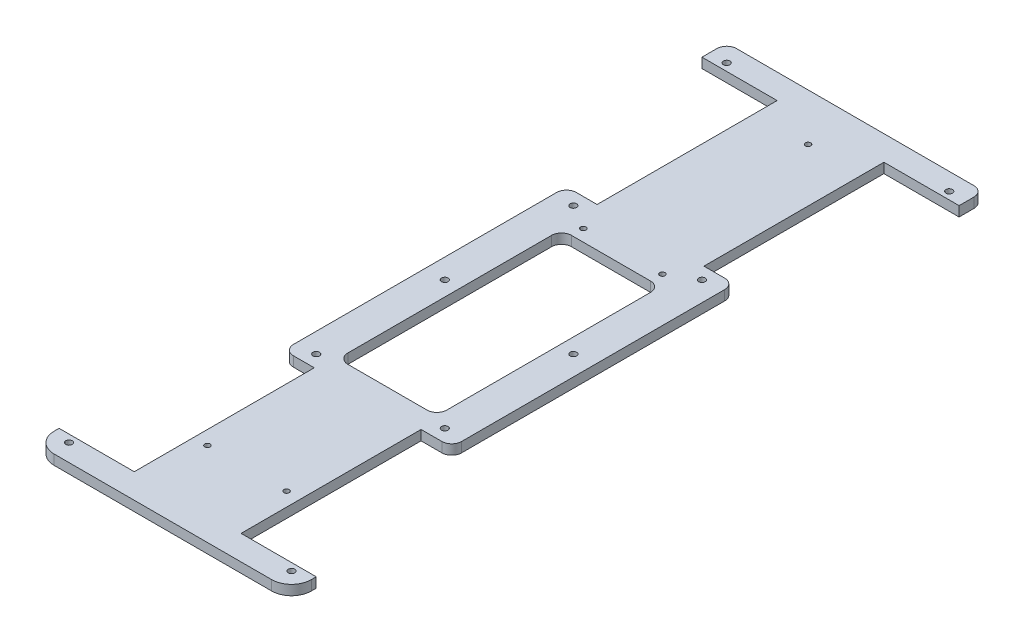
SolidWorks part; units mm, degrees
ref_plane "Front Plane" through (0, 0, 0) normal (0, 0, 1) x (1, 0, 0)
ref_plane "Top Plane" through (0, 0, 0) normal (0, 1, 0) x (1, 0, 0)
ref_plane "Right Plane" through (0, 0, 0) normal (1, 0, 0) x (0, 0, -1)
sketch "Sketch1" plane through (0, 0, 0) normal (0, 1, 0) x (1, 0, 0)
  line L0 (0, 0) -> (130, 0)
  line L1 (0, 0) -> (130, 0) construction
  line L2 (0, 0) -> (0, 350) construction
  line L3 (0, 350) -> (130, 350) construction
  line L4 (130, 0) -> (130, 350) construction
  line L5 (130, 0) -> (130, 12.5)
  line L6 (130, 12.5) -> (92, 12.5)
  line L7 (92, 12.5) -> (92, 103.5)
  line L11 (92, 246.5) -> (92, 337.5)
  line L12 (92, 337.5) -> (130, 337.5)
  line L13 (130, 337.5) -> (130, 350)
  line L14 (130, 350) -> (0, 350)
  line L15 (0, 350) -> (0, 337.5)
  line L16 (0, 337.5) -> (38, 337.5)
  line L17 (38, 337.5) -> (38, 246.5)
  line L21 (38, 103.5) -> (38, 12.5)
  line L22 (38, 12.5) -> (0, 12.5)
  line L23 (0, 12.5) -> (0, 0)
  line L24 (38, 246.5) -> (22.5, 246.5)
  line L25 (22.5, 246.5) -> (22.5, 103.5)
  line L26 (22.5, 103.5) -> (38, 103.5)
  line L27 (92, 246.5) -> (107.5, 246.5)
  line L28 (107.5, 246.5) -> (107.5, 103.5)
  line L29 (107.5, 103.5) -> (92, 103.5)
  dimension "D1" = 130
  dimension "D2" = 350
  dimension "D3" = 38
  dimension "D4" = 91
  dimension "D5" = 22.5
  dimension "D6" = 143
extrude "Boss-Extrude1" add sketch "Sketch1" along normal blind 5
fillet "Fillet1" radius 10 2 edges at (130, 2.5, 0) (0, 2.5, 0)
fillet "Fillet2" radius 5 6 edges at (0, 2.5, -350) (130, 2.5, -350) (107.5, 2.5, -246.5) (107.5, 2.5, -103.5) (22.5, 2.5, -103.5) (22.5, 2.5, -246.5)
sketch "Sketch2" plane through (0, 5, 0) normal (0, 1, 0) x (1, 0, 0)
  line L2 (32.5, 240) -> (32.5, 110) construction
  line L3 (22.5, 175) -> (32.5, 175) construction
  line L4 (22.5, 241.5) -> (22.5, 108.5) construction
  line L5 (65, 350) -> (65, 0) construction
  line L6 (125, 350) -> (5, 350) construction
  line L7 (10, 0) -> (120, 0) construction
  circle A0 centre (32.5, 240) radius 1.65
  circle A1 centre (32.5, 175) radius 1.65
  circle A2 centre (32.5, 110) radius 1.65
  circle A3 centre (97.5, 110) radius 1.65
  circle A4 centre (97.5, 175) radius 1.65
  circle A5 centre (97.5, 240) radius 1.65
  dimension "D3" = 3.3
  dimension "D1" = 10
  dimension "D2" = 130
extrude "Cut-Extrude1" cut sketch "Sketch2" against normal through all
sketch "Sketch3" plane through (0, 5, 0) normal (0, 1, 0) x (1, 0, 0)
  line L0 (0, 12.5) -> (8.75, 12.5) construction
  line L1 (38, 12.5) -> (0, 12.5) construction
  line L2 (8.75, 12.5) -> (8.75, 8.75) construction
  line L3 (65, 0) -> (65, 57.6288) construction
  line L4 (10, 0) -> (120, 0) construction
  circle A0 centre (8.75, 8.75) radius 1.65
  circle A1 centre (121.25, 8.75) radius 1.65
  dimension "D3" = 3.3
  dimension "D1" = 8.75
  dimension "D2" = 3.75
extrude "Cut-Extrude2" cut sketch "Sketch3" against normal through all
sketch "Sketch4" plane through (0, 5, 0) normal (0, 1, 0) x (1, 0, 0)
  line L0 (0, 337.5) -> (8.75, 337.5) construction
  line L1 (0, 337.5) -> (38, 337.5) construction
  line L2 (8.75, 337.5) -> (8.75, 341.25) construction
  line L3 (65, 350) -> (65, 288.2737) construction
  line L4 (125, 350) -> (5, 350) construction
  circle A0 centre (8.75, 341.25) radius 1.65
  circle A1 centre (121.25, 341.25) radius 1.65
  dimension "D3" = 3.3
  dimension "D1" = 8.75
  dimension "D2" = 3.75
extrude "Cut-Extrude3" cut sketch "Sketch4" against normal through all
sketch "Sketch5" plane through (0, 5, 0) normal (0, 1, 0) x (1, 0, 0)
  line L0 (38, 12.5) -> (92, 12.5) construction
  line L1 (65, 12.5) -> (65, 42.5) construction
  line L2 (45, 42.5) -> (85, 42.5) construction
  line L3 (65, 42.5) -> (65, 232.5) construction
  line L4 (45, 232.5) -> (85, 232.5) construction
  line L5 (65, 350) -> (65, 326.15) construction
  line L6 (125, 350) -> (5, 350) construction
  circle A0 centre (45, 42.5) radius 1.35
  circle A1 centre (85, 42.5) radius 1.35
  circle A2 centre (45, 232.5) radius 1.35
  circle A3 centre (85, 232.5) radius 1.35
  circle A4 centre (65, 326.15) radius 1.35
  point P8 (65, 42.5)
  point P14 (65, 232.5)
  dimension "D3" = 2.7
  dimension "D1" = 30
  dimension "D2" = 40
  dimension "D4" = 190
  dimension "D5" = 40
  dimension "D6" = 23.85
extrude "Cut-Extrude4" cut sketch "Sketch5" against normal blind 10
sketch "Sketch6" plane through (0, 5, 0) normal (0, 1, 0) x (1, 0, 0)
  line L0 (38, 246.5) -> (92, 246.5) construction
  line L1 (40, 226.5) -> (90, 226.5)
  line L2 (40, 226.5) -> (40, 113.5)
  line L3 (40, 113.5) -> (90, 113.5)
  line L4 (90, 226.5) -> (90, 113.5)
  line L5 (38, 103.5) -> (92, 103.5) construction
  line L6 (65, 246.5) -> (65, 103.5) construction
  point P13 (65, 113.5)
  point P16 (65, 103.5)
  dimension "D1" = 20
  dimension "D2" = 10
  dimension "D3" = 50
extrude "Cut-Extrude5" cut sketch "Sketch6" against normal blind 10
fillet "Fillet4" radius 5 4 edges at (90, 2.5, -113.5) (40, 2.5, -113.5) (90, 2.5, -226.5) (40, 2.5, -226.5)
